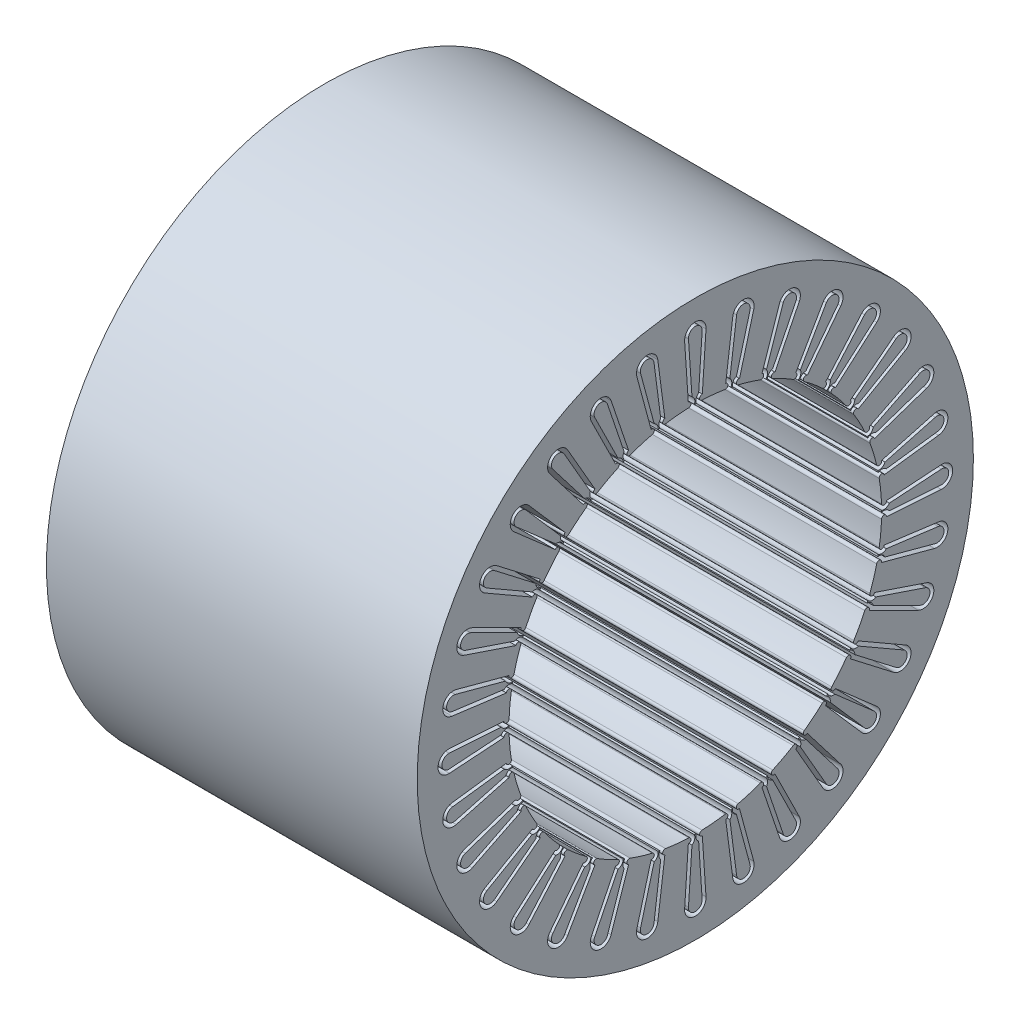
SolidWorks part; units mm, degrees
ref_plane "Front Plane" through (0, 0, 0) normal (0, 0, 1) x (1, 0, 0)
ref_plane "Top Plane" through (0, 0, 0) normal (0, 1, 0) x (1, 0, 0)
ref_plane "Right Plane" through (0, 0, 0) normal (1, 0, 0) x (0, 0, -1)
sketch "Sketch1" plane through (0, 0, 0) normal (1, 0, 0) x (0, 0, -1)
  circle A0 centre (0, 0) radius 150
  circle A1 centre (0, 0) radius 100.5
  dimension "D1" = 201
  dimension "D2" = 300
extrude "Boss-Extrude1" add sketch "Sketch1" along normal blind 200
sketch "Sketch2" plane through (200, 0, 0) normal (1, 0, 0) x (0, 0, -1)
  line L0 (0, 168.649) -> (0, -183.7787) construction
  line L1 (224.223, 0) -> (-272.8884, 0) construction
  line L2 (5.7644, 132.6209) -> (3.7812, 103.1555)
  line L5 (-5.7644, 132.6209) -> (-3.7812, 103.1555)
  line L6 (20.2194, 131.1972) -> (16.4161, 101.9111)
  line L7 (31.5267, 128.948) -> (23.8332, 100.4358)
  line L8 (45.4262, 124.7317) -> (35.9825, 96.7503)
  line L9 (56.0775, 120.3197) -> (42.9693, 93.8563)
  line L10 (68.8872, 113.4728) -> (54.1662, 87.8714)
  line L11 (78.4732, 107.0677) -> (60.4541, 83.67)
  line L12 (89.701, 97.8532) -> (70.2683, 75.6157)
  line L13 (97.8532, 89.701) -> (75.6157, 70.2683)
  line L14 (107.0677, 78.4732) -> (83.67, 60.4541)
  line L15 (113.4728, 68.8872) -> (87.8714, 54.1662)
  line L16 (120.3197, 56.0775) -> (93.8563, 42.9693)
  line L17 (124.7317, 45.4262) -> (96.7503, 35.9825)
  line L18 (128.948, 31.5267) -> (100.4358, 23.8332)
  line L19 (131.1972, 20.2194) -> (101.9111, 16.4161)
  line L20 (132.6209, 5.7644) -> (103.1555, 3.7812)
  line L21 (132.6209, -5.7644) -> (103.1555, -3.7812)
  line L22 (131.1972, -20.2194) -> (101.9111, -16.4161)
  line L23 (128.948, -31.5267) -> (100.4358, -23.8332)
  line L24 (124.7317, -45.4262) -> (96.7503, -35.9825)
  line L25 (120.3197, -56.0775) -> (93.8563, -42.9693)
  line L26 (113.4728, -68.8872) -> (87.8714, -54.1662)
  line L27 (107.0677, -78.4732) -> (83.67, -60.4541)
  line L28 (97.8532, -89.701) -> (75.6157, -70.2683)
  line L29 (89.701, -97.8532) -> (70.2683, -75.6157)
  line L30 (78.4732, -107.0677) -> (60.4541, -83.67)
  line L31 (68.8872, -113.4728) -> (54.1662, -87.8714)
  line L32 (56.0775, -120.3197) -> (42.9693, -93.8563)
  line L33 (45.4262, -124.7317) -> (35.9825, -96.7503)
  line L34 (31.5267, -128.948) -> (23.8332, -100.4358)
  line L35 (20.2194, -131.1972) -> (16.4161, -101.9111)
  line L36 (5.7644, -132.6209) -> (3.7812, -103.1555)
  line L37 (-5.7644, -132.6209) -> (-3.7812, -103.1555)
  line L38 (-20.2194, -131.1972) -> (-16.4161, -101.9111)
  line L39 (-31.5267, -128.948) -> (-23.8332, -100.4358)
  line L40 (-45.4262, -124.7317) -> (-35.9825, -96.7503)
  line L41 (-56.0775, -120.3197) -> (-42.9693, -93.8563)
  line L42 (-68.8872, -113.4728) -> (-54.1662, -87.8714)
  line L43 (-78.4732, -107.0677) -> (-60.4541, -83.67)
  line L44 (-89.701, -97.8532) -> (-70.2683, -75.6157)
  line L45 (-97.8532, -89.701) -> (-75.6157, -70.2683)
  line L46 (-107.0677, -78.4732) -> (-83.67, -60.4541)
  line L47 (-113.4728, -68.8872) -> (-87.8714, -54.1662)
  line L48 (-120.3197, -56.0775) -> (-93.8563, -42.9693)
  line L49 (-124.7317, -45.4262) -> (-96.7503, -35.9825)
  line L50 (-128.948, -31.5267) -> (-100.4358, -23.8332)
  line L51 (-131.1972, -20.2194) -> (-101.9111, -16.4161)
  line L52 (-132.6209, -5.7644) -> (-103.1555, -3.7812)
  line L53 (-132.6209, 5.7644) -> (-103.1555, 3.7812)
  line L54 (-131.1972, 20.2194) -> (-101.9111, 16.4161)
  line L55 (-128.948, 31.5267) -> (-100.4358, 23.8332)
  line L56 (-124.7317, 45.4262) -> (-96.7503, 35.9825)
  line L57 (-120.3197, 56.0775) -> (-93.8563, 42.9693)
  line L58 (-113.4728, 68.8872) -> (-87.8714, 54.1662)
  line L59 (-107.0677, 78.4732) -> (-83.67, 60.4541)
  line L60 (-97.8532, 89.701) -> (-75.6157, 70.2683)
  line L61 (-89.701, 97.8532) -> (-70.2683, 75.6157)
  line L62 (-78.4732, 107.0677) -> (-60.4541, 83.67)
  line L63 (-68.8872, 113.4728) -> (-54.1662, 87.8714)
  line L64 (-56.0775, 120.3197) -> (-42.9693, 93.8563)
  line L65 (-45.4262, 124.7317) -> (-35.9825, 96.7503)
  line L66 (-31.5267, 128.948) -> (-23.8332, 100.4358)
  line L67 (-20.2194, 131.1972) -> (-16.4161, 101.9111)
  arc A10 (5.7644, 132.6209) -> (-5.7644, 132.6209) centre (0, 133.0089) ccw
  circle A12 centre (0, 0) radius 100.5 construction
  arc A14 (-3.6897, 100.4322) -> (-3.7812, 103.1555) centre (-3.6897, 101.7954) ccw
  arc A15 (3.6897, 100.4322) -> (3.7812, 103.1555) centre (3.6897, 101.7954) cw
  arc A16 (15.9746, 99.2223) -> (16.4161, 101.9111) centre (16.2405, 100.5593) ccw
  arc A17 (23.2121, 97.7827) -> (23.8332, 100.4358) centre (23.4781, 99.1196) cw
  arc A18 (31.5267, 128.948) -> (20.2194, 131.1972) centre (25.9487, 130.4531) ccw
  arc A19 (35.025, 94.1993) -> (35.9825, 96.7503) centre (35.5466, 95.4587) ccw
  arc A20 (41.8426, 91.3753) -> (42.9693, 93.8563) centre (42.3642, 92.6347) cw
  arc A21 (56.0775, 120.3197) -> (45.4262, 124.7317) centre (50.9003, 122.8842) ccw
  arc A22 (52.7293, 85.5562) -> (54.1662, 87.8714) centre (53.4867, 86.6897) ccw
  arc A23 (58.865, 81.4565) -> (60.4541, 83.67) centre (59.6223, 82.5899) cw
  arc A24 (78.4732, 107.0677) -> (68.8872, 113.4728) centre (73.8958, 110.5928) ccw
  arc A25 (68.4073, 73.6253) -> (70.2683, 75.6157) centre (69.3713, 74.5892) ccw
  arc A26 (73.6253, 68.4073) -> (75.6157, 70.2683) centre (74.5892, 69.3713) cw
  arc A27 (97.8532, 89.701) -> (89.701, 97.8532) centre (94.0515, 94.0515) ccw
  arc A28 (81.4565, 58.865) -> (83.67, 60.4541) centre (82.5899, 59.6223) ccw
  arc A29 (85.5562, 52.7293) -> (87.8714, 54.1662) centre (86.6897, 53.4867) cw
  arc A30 (113.4728, 68.8872) -> (107.0677, 78.4732) centre (110.5928, 73.8958) ccw
  arc A31 (91.3753, 41.8426) -> (93.8563, 42.9693) centre (92.6347, 42.3642) ccw
  arc A32 (94.1993, 35.025) -> (96.7503, 35.9825) centre (95.4587, 35.5466) cw
  arc A33 (124.7317, 45.4262) -> (120.3197, 56.0775) centre (122.8842, 50.9003) ccw
  arc A34 (97.7827, 23.2121) -> (100.4358, 23.8332) centre (99.1196, 23.4781) ccw
  arc A35 (99.2223, 15.9746) -> (101.9111, 16.4161) centre (100.5593, 16.2405) cw
  arc A36 (131.1972, 20.2194) -> (128.948, 31.5267) centre (130.4531, 25.9487) ccw
  arc A37 (100.4322, 3.6897) -> (103.1555, 3.7812) centre (101.7954, 3.6897) ccw
  arc A38 (100.4322, -3.6897) -> (103.1555, -3.7812) centre (101.7954, -3.6897) cw
  arc A39 (132.6209, -5.7644) -> (132.6209, 5.7644) centre (133.0089, 0) ccw
  arc A40 (99.2223, -15.9746) -> (101.9111, -16.4161) centre (100.5593, -16.2405) ccw
  arc A41 (97.7827, -23.2121) -> (100.4358, -23.8332) centre (99.1196, -23.4781) cw
  arc A42 (128.948, -31.5267) -> (131.1972, -20.2194) centre (130.4531, -25.9487) ccw
  arc A43 (94.1993, -35.025) -> (96.7503, -35.9825) centre (95.4587, -35.5466) ccw
  arc A44 (91.3753, -41.8426) -> (93.8563, -42.9693) centre (92.6347, -42.3642) cw
  arc A45 (120.3197, -56.0775) -> (124.7317, -45.4262) centre (122.8842, -50.9003) ccw
  arc A46 (85.5562, -52.7293) -> (87.8714, -54.1662) centre (86.6897, -53.4867) ccw
  arc A47 (81.4565, -58.865) -> (83.67, -60.4541) centre (82.5899, -59.6223) cw
  arc A48 (107.0677, -78.4732) -> (113.4728, -68.8872) centre (110.5928, -73.8958) ccw
  arc A49 (73.6253, -68.4073) -> (75.6157, -70.2683) centre (74.5892, -69.3713) ccw
  arc A50 (68.4073, -73.6253) -> (70.2683, -75.6157) centre (69.3713, -74.5892) cw
  arc A51 (89.701, -97.8532) -> (97.8532, -89.701) centre (94.0515, -94.0515) ccw
  arc A52 (58.865, -81.4565) -> (60.4541, -83.67) centre (59.6223, -82.5899) ccw
  arc A53 (52.7293, -85.5562) -> (54.1662, -87.8714) centre (53.4867, -86.6897) cw
  arc A54 (68.8872, -113.4728) -> (78.4732, -107.0677) centre (73.8958, -110.5928) ccw
  arc A55 (41.8426, -91.3753) -> (42.9693, -93.8563) centre (42.3642, -92.6347) ccw
  arc A56 (35.025, -94.1993) -> (35.9825, -96.7503) centre (35.5466, -95.4587) cw
  arc A57 (45.4262, -124.7317) -> (56.0775, -120.3197) centre (50.9003, -122.8842) ccw
  arc A58 (23.2121, -97.7827) -> (23.8332, -100.4358) centre (23.4781, -99.1196) ccw
  arc A59 (15.9746, -99.2223) -> (16.4161, -101.9111) centre (16.2405, -100.5593) cw
  arc A60 (20.2194, -131.1972) -> (31.5267, -128.948) centre (25.9487, -130.4531) ccw
  arc A61 (3.6897, -100.4322) -> (3.7812, -103.1555) centre (3.6897, -101.7954) ccw
  arc A62 (-3.6897, -100.4322) -> (-3.7812, -103.1555) centre (-3.6897, -101.7954) cw
  arc A63 (-5.7644, -132.6209) -> (5.7644, -132.6209) centre (0, -133.0089) ccw
  arc A64 (-15.9746, -99.2223) -> (-16.4161, -101.9111) centre (-16.2405, -100.5593) ccw
  arc A65 (-23.2121, -97.7827) -> (-23.8332, -100.4358) centre (-23.4781, -99.1196) cw
  arc A66 (-31.5267, -128.948) -> (-20.2194, -131.1972) centre (-25.9487, -130.4531) ccw
  arc A67 (-35.025, -94.1993) -> (-35.9825, -96.7503) centre (-35.5466, -95.4587) ccw
  arc A68 (-41.8426, -91.3753) -> (-42.9693, -93.8563) centre (-42.3642, -92.6347) cw
  arc A69 (-56.0775, -120.3197) -> (-45.4262, -124.7317) centre (-50.9003, -122.8842) ccw
  arc A70 (-52.7293, -85.5562) -> (-54.1662, -87.8714) centre (-53.4867, -86.6897) ccw
  arc A71 (-58.865, -81.4565) -> (-60.4541, -83.67) centre (-59.6223, -82.5899) cw
  arc A72 (-78.4732, -107.0677) -> (-68.8872, -113.4728) centre (-73.8958, -110.5928) ccw
  arc A73 (-68.4073, -73.6253) -> (-70.2683, -75.6157) centre (-69.3713, -74.5892) ccw
  arc A74 (-73.6253, -68.4073) -> (-75.6157, -70.2683) centre (-74.5892, -69.3713) cw
  arc A75 (-97.8532, -89.701) -> (-89.701, -97.8532) centre (-94.0515, -94.0515) ccw
  arc A76 (-81.4565, -58.865) -> (-83.67, -60.4541) centre (-82.5899, -59.6223) ccw
  arc A77 (-85.5562, -52.7293) -> (-87.8714, -54.1662) centre (-86.6897, -53.4867) cw
  arc A78 (-113.4728, -68.8872) -> (-107.0677, -78.4732) centre (-110.5928, -73.8958) ccw
  arc A79 (-91.3753, -41.8426) -> (-93.8563, -42.9693) centre (-92.6347, -42.3642) ccw
  arc A80 (-94.1993, -35.025) -> (-96.7503, -35.9825) centre (-95.4587, -35.5466) cw
  arc A81 (-124.7317, -45.4262) -> (-120.3197, -56.0775) centre (-122.8842, -50.9003) ccw
  arc A82 (-97.7827, -23.2121) -> (-100.4358, -23.8332) centre (-99.1196, -23.4781) ccw
  arc A83 (-99.2223, -15.9746) -> (-101.9111, -16.4161) centre (-100.5593, -16.2405) cw
  arc A84 (-131.1972, -20.2194) -> (-128.948, -31.5267) centre (-130.4531, -25.9487) ccw
  arc A85 (-100.4322, -3.6897) -> (-103.1555, -3.7812) centre (-101.7954, -3.6897) ccw
  arc A86 (-100.4322, 3.6897) -> (-103.1555, 3.7812) centre (-101.7954, 3.6897) cw
  arc A87 (-132.6209, 5.7644) -> (-132.6209, -5.7644) centre (-133.0089, 0) ccw
  arc A88 (-99.2223, 15.9746) -> (-101.9111, 16.4161) centre (-100.5593, 16.2405) ccw
  arc A89 (-97.7827, 23.2121) -> (-100.4358, 23.8332) centre (-99.1196, 23.4781) cw
  arc A90 (-128.948, 31.5267) -> (-131.1972, 20.2194) centre (-130.4531, 25.9487) ccw
  arc A91 (-94.1993, 35.025) -> (-96.7503, 35.9825) centre (-95.4587, 35.5466) ccw
  arc A92 (-91.3753, 41.8426) -> (-93.8563, 42.9693) centre (-92.6347, 42.3642) cw
  arc A93 (-120.3197, 56.0775) -> (-124.7317, 45.4262) centre (-122.8842, 50.9003) ccw
  arc A94 (-85.5562, 52.7293) -> (-87.8714, 54.1662) centre (-86.6897, 53.4867) ccw
  arc A95 (-81.4565, 58.865) -> (-83.67, 60.4541) centre (-82.5899, 59.6223) cw
  arc A96 (-107.0677, 78.4732) -> (-113.4728, 68.8872) centre (-110.5928, 73.8958) ccw
  arc A97 (-73.6253, 68.4073) -> (-75.6157, 70.2683) centre (-74.5892, 69.3713) ccw
  arc A98 (-68.4073, 73.6253) -> (-70.2683, 75.6157) centre (-69.3713, 74.5892) cw
  arc A99 (-89.701, 97.8532) -> (-97.8532, 89.701) centre (-94.0515, 94.0515) ccw
  arc A100 (-58.865, 81.4565) -> (-60.4541, 83.67) centre (-59.6223, 82.5899) ccw
  arc A101 (-52.7293, 85.5562) -> (-54.1662, 87.8714) centre (-53.4867, 86.6897) cw
  arc A102 (-68.8872, 113.4728) -> (-78.4732, 107.0677) centre (-73.8958, 110.5928) ccw
  arc A103 (-41.8426, 91.3753) -> (-42.9693, 93.8563) centre (-42.3642, 92.6347) ccw
  arc A104 (-35.025, 94.1993) -> (-35.9825, 96.7503) centre (-35.5466, 95.4587) cw
  arc A105 (-45.4262, 124.7317) -> (-56.0775, 120.3197) centre (-50.9003, 122.8842) ccw
  arc A106 (-23.2121, 97.7827) -> (-23.8332, 100.4358) centre (-23.4781, 99.1196) ccw
  arc A107 (-15.9746, 99.2223) -> (-16.4161, 101.9111) centre (-16.2405, 100.5593) cw
  arc A108 (-20.2194, 131.1972) -> (-31.5267, 128.948) centre (-25.9487, 130.4531) ccw
  point P297 (0, 0)
extrude "Cut-Extrude-Thin3" cut sketch "Sketch2" against normal blind 200 thin thin type one direction reverse wall 2.08
